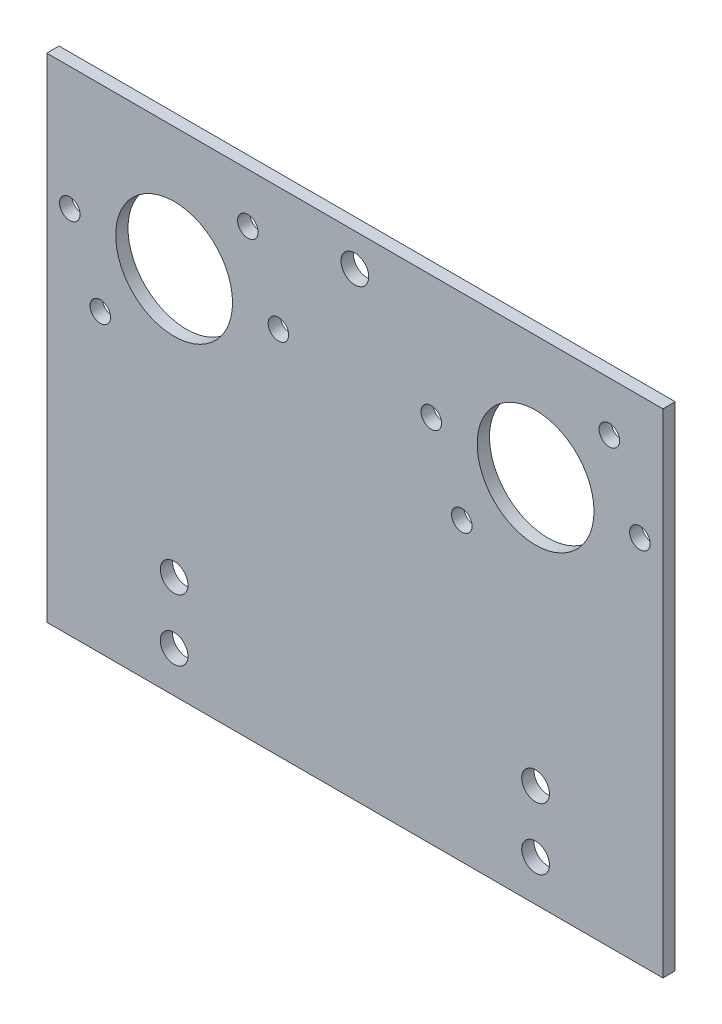
SolidWorks part; units mm, degrees
ref_plane "Front Plane" through (0, 0, 0) normal (0, 0, 1) x (1, 0, 0)
ref_plane "Top Plane" through (0, 0, 0) normal (0, 1, 0) x (1, 0, 0)
ref_plane "Right Plane" through (0, 0, 0) normal (1, 0, 0) x (0, 0, -1)
sketch "Sketch1" plane through (0, 0, 0) normal (0, 0, 1) x (1, 0, 0)
  line L1 (0, 0) -> (150, 0)
  line L2 (0, 0) -> (0, -120)
  line L3 (0, -120) -> (150, -120)
  line L4 (150, 0) -> (150, -120)
  dimension "D1" = 120
  dimension "D2" = 150
extrude "Boss-Extrude1" add sketch "Sketch1" along normal blind 3
sketch "Sketch2" plane through (0, 0, 3) normal (0, 0, 1) x (1, 0, 0)
  line L0 (0, 0) -> (0, -120) construction
  line L1 (150, -120) -> (150, 0) construction
  line L2 (0, -120) -> (150, -120) construction
  line L3 (150, 0) -> (0, 0) construction
  circle A0 centre (31, -30) radius 14.225
  circle A1 centre (119, -30) radius 14.225
  circle A2 centre (31, -110) radius 3.375
  circle A5 centre (119, -110) radius 3.375
  circle A7 centre (75, -8) radius 3.375
  circle A8 centre (31, -95) radius 3.375
  circle A9 centre (119, -95) radius 3.375
  dimension "D1" = 28.45
  dimension "D2" = 28.45
  dimension "D3" = 6.75
  dimension "D4" = 30
  dimension "D5" = 6.75
  dimension "D7" = 15
  dimension "D8" = 6.75
  dimension "D9" = 31
  dimension "D10" = 31
  dimension "D11" = 75
  dimension "D13" = 15
  dimension "D14" = 10
  dimension "D16" = 8
extrude "Cut-Extrude1" cut sketch "Sketch2" against normal through all
sketch "Sketch3" plane through (0, 0, 0) normal (0, 0, -1) x (-1, 0, 0)
  circle A0 centre (-13.0395, -47.9605) radius 2.0193 construction
  circle A1 centre (-56.4, -30) radius 2.0193 construction
  circle A2 centre (-48.9605, -12.0395) radius 2.0193 construction
  circle A3 centre (-13.0395, -47.9605) radius 2.0193
  circle A4 centre (-56.4, -30) radius 2.0193
  circle A5 centre (-48.9605, -12.0395) radius 2.0193
  circle A6 centre (-5.6, -30) radius 2.0193 construction
  circle A7 centre (-5.6, -30) radius 2.0193
  circle A8 centre (-136.9605, -12.0395) radius 2.0193 construction
  circle A9 centre (-144.4, -30) radius 2.0193 construction
  circle A10 centre (-136.9605, -12.0395) radius 2.0193
  circle A11 centre (-144.4, -30) radius 2.0193
  circle A12 centre (-93.6, -30) radius 2.0193 construction
  circle A13 centre (-101.0395, -47.9605) radius 2.0193 construction
  circle A14 centre (-93.6, -30) radius 2.0193
  circle A15 centre (-101.0395, -47.9605) radius 2.0193
  point P25 (-5.6, -30)
  point P26 (-13.0395, -47.9605)
  point P27 (-56.4, -30)
  point P28 (-48.9605, -12.0395)
  point P29 (-93.6, -30)
  point P30 (-101.0395, -47.9605)
  point P31 (-144.4, -30)
  point P32 (-136.9605, -12.0395)
extrude "Cut-Extrude2" cut sketch "Sketch3" against normal through all
sketch "Sketch6" plane through (0, 0, 3) normal (0, 0, 1) x (1, 0, 0)
  circle A0 centre (5.6, -30) radius 2.5
  circle A1 centre (13.0395, -47.9605) radius 2.5
  circle A3 centre (56.4, -30) radius 2.5
  circle A4 centre (48.9605, -12.0395) radius 2.5
  circle A5 centre (101.0395, -47.9605) radius 2.5
  circle A6 centre (93.6, -30) radius 2.5
  circle A7 centre (136.9605, -12.0395) radius 2.5
  circle A8 centre (144.4, -30) radius 2.5
  dimension "D1" = 5
  dimension "D2" = 5
  dimension "D3" = 5
  dimension "D4" = 5
  dimension "D5" = 5
  dimension "D6" = 5
  dimension "D7" = 5
  dimension "D8" = 5
extrude "Cut-Extrude3" cut sketch "Sketch6" against normal through all
